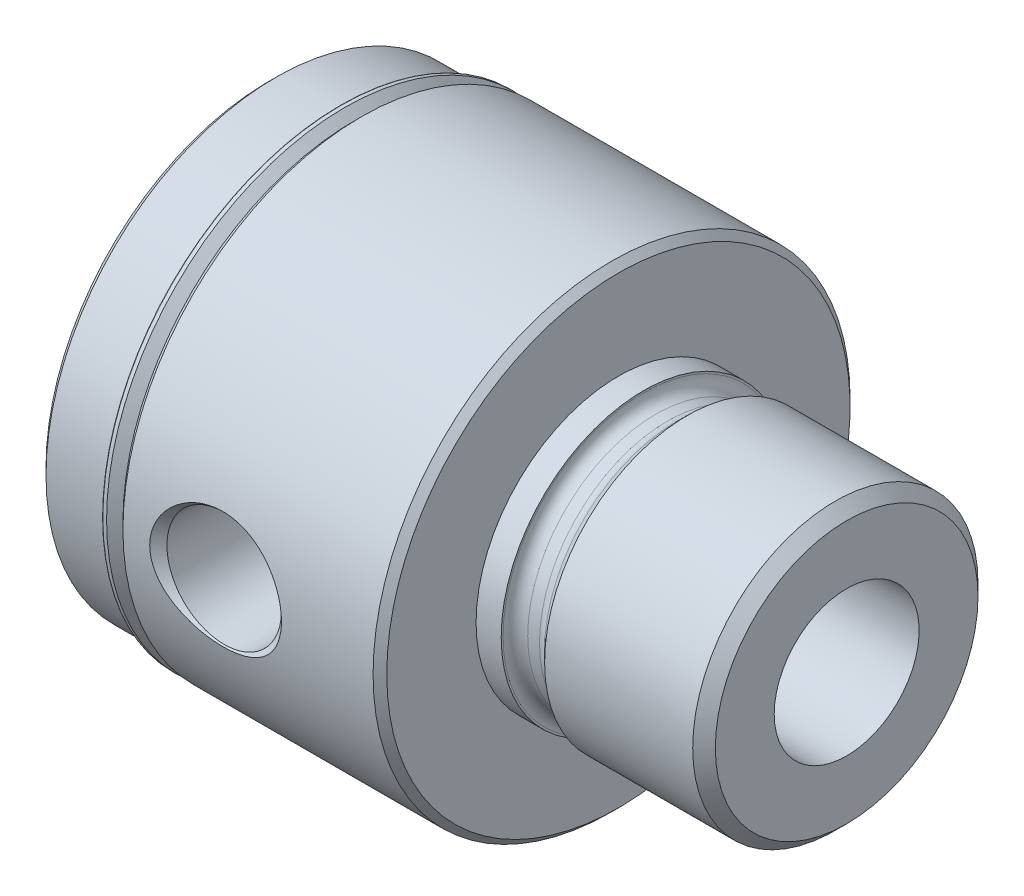
SolidWorks part; units mm, degrees
ref_plane "Front Plane" through (0, 0, 0) normal (0, 0, 1) x (1, 0, 0)
ref_plane "Top Plane" through (0, 0, 0) normal (0, 1, 0) x (1, 0, 0)
ref_plane "Right Plane" through (0, 0, 0) normal (1, 0, 0) x (0, 0, -1)
sketch "Sketch1" plane through (0, 0, 0) normal (0, 0, 1) x (1, 0, 0)
  line L0 (-38.8874, 0) -> (-38.8874, 24.8158)
  line L1 (-38.8874, 24.8158) -> (-38.1254, 25.5778)
  line L2 (-38.1254, 25.5778) -> (-31.496, 25.5778)
  line L3 (-31.496, 25.5778) -> (-30.4292, 24.511)
  line L4 (-30.4292, 24.511) -> (-29.3624, 24.511)
  line L5 (-29.3624, 24.511) -> (-29.3624, 25.781)
  line L6 (-29.3624, 25.781) -> (-28.6004, 26.543)
  line L7 (-28.6004, 26.543) -> (-0.762, 26.543)
  line L8 (-0.762, 26.543) -> (0, 25.781)
  line L9 (0, 25.781) -> (0, 0)
  line L10 (0, 0) -> (-38.8874, 0)
  line L11 (0, 0) -> (-38.8874, 0) construction
revolve "Revolve1" add sketch "Sketch1" angle 360 about L11 reverse direction yes
sketch "Sketch2" plane through (0, 0, 0) normal (0, 0, 1) x (1, 0, 0)
  line L0 (0, 0) -> (0, 15.8432)
  line L1 (0, 15.8432) -> (2.794, 15.8432)
  line L2 (2.794, 15.8432) -> (2.794, 15.6337)
  line L3 (4.1656, 14.2621) -> (5.4771, 14.2621)
  line L4 (6.4469, 14.6638) -> (7.6581, 15.875)
  line L5 (7.6581, 15.875) -> (24.1402, 15.875)
  line L6 (24.1402, 15.875) -> (25.4, 14.6152)
  line L7 (25.4, 14.6152) -> (25.4, 0)
  line L8 (25.4, 0) -> (0, 0)
  line L9 (25.4, 0) -> (0, 0) construction
  arc A0 (2.794, 15.6337) -> (4.1656, 14.2621) centre (4.1656, 15.6337) ccw
  arc A1 (5.4771, 14.2621) -> (6.4469, 14.6638) centre (5.4771, 15.6337) ccw
revolve "Revolve2" add sketch "Sketch2" angle 360 about L9 reverse direction yes
cosmetic thread "Cosmetic Thread1" parameters "D1"=18.9531, "D2"=29.2303
sketch "Sketch3" plane through (0, 0, 0) normal (0, 1, 0) x (1, 0, 0)
  line L0 (-18.288, 0) -> (-12.6123, -3.2768)
  line L1 (-12.6123, -3.2768) -> (-11.9159, -25.5856)
  line L2 (-11.9159, -25.5856) -> (-10.9585, -26.543)
  line L3 (-10.9585, -26.543) -> (-10.9585, -29.083)
  line L4 (-10.9585, -29.083) -> (-18.288, -29.083)
  line L5 (-18.288, -29.083) -> (-18.288, 0)
  line L6 (-18.288, -29.083) -> (-18.288, 0) construction
revolve "Cut-Revolve1" cut sketch "Sketch3" angle 360 about L6 reverse direction yes
cosmetic thread "Cosmetic Thread2" parameters "D1"=20.574, "D2"=40.1763
sketch "Sketch4" plane through (0, 0, 0) normal (0, 0, 1) x (1, 0, 0)
  line L0 (-30.9438, 26.3188) -> (-28.8128, 24.1877)
  line L1 (-28.8128, 24.1877) -> (-28.4895, 24.511)
  line L2 (-28.4895, 24.511) -> (-30.4707, 26.4922)
  line L3 (-30.4707, 26.4922) -> (-30.872, 26.4922)
  line L4 (-30.4707, 0) -> (-31.1172, 0) construction
  arc A0 (-30.872, 26.4922) -> (-30.9438, 26.3188) centre (-30.872, 26.3906) ccw
revolve "Revolve3" add sketch "Sketch4" angle 360 about L4 reverse direction yes
ref_plane "Plane1" through (-26.1874, 0, 0) normal (1, 0, 0) x (0, 0, -1)
ref_plane "Plane2" through (35.0266, 0, 0) normal (1, 0, 0) x (0, 0, -1)
ref_plane "Plane3" through (15.9766, 0, 0) normal (1, 0, 0) x (0, 0, -1)
ref_plane "Plane4" through (-9.4234, 0, 0) normal (1, 0, 0) x (0, 0, -1)
ref_plane "Plane5" through (-9.4234, 0, 0) normal (1, 0, 0) x (0, 0, -1)
sketch "Sketch5" plane through (0, 0, 0) normal (0, 0, 1) x (1, 0, 0)
  line L0 (-38.8874, 0) -> (-38.8874, 8.0645)
  line L1 (-38.8874, 8.0645) -> (35.052, 8.0645)
  line L2 (35.052, 8.0645) -> (35.052, 0)
  line L3 (35.052, 0) -> (-38.8874, 0)
  line L4 (35.052, 0) -> (-38.8874, 0) construction
revolve "Cut-Revolve2" cut sketch "Sketch5" angle 360 about L4 reverse direction yes
ref_plane "Plane6" through (-38.8874, 0, 0) normal (1, 0, 0) x (0, 0, -1)
ref_plane "Plane7" through (25.4, 0, 0) normal (1, 0, 0) x (0, 0, -1)
ref_plane "Plane8" through (25.4, 0, 0) normal (1, 0, 0) x (0, 0, -1)
ref_plane "Plane9" through (0, 0, 0) normal (0, 0, 1) x (1, 0, 0)
ref_plane "Plane10" through (0, 0, 0) normal (1, 0, 0) x (0, 0, -1)
ref_plane "Plane11" through (25.4, 0, 0) normal (1, 0, 0) x (0, 0, -1)
ref_plane "e2 XY" through (0, 0, 0) normal (0, 0, 1) x (1, 0, 0)
ref_plane "e2 XZ" through (0, 0, 0) normal (0, -1, 0) x (-1, 0, 0)
ref_plane "e2 YZ" through (-18.288, 0, 0) normal (1, 0, 0) x (0, 0, -1)
ref_axis "e2 X" through (-80.9, 0, 0) along (1, 0, 0)
ref_axis "e2 Y" through (-18.288, -50, 0) along (0, 1, 0)
ref_axis "e2 Z" through (-18.288, 0, 80.9) along (0, 0, -1)
sketch3d "e2"
  point P0 (-18.288, 0, 0)
ref_plane "g2 XY" through (0, 0, 0) normal (0, 0, 1) x (1, 0, 0)
ref_plane "g2 XZ" through (0, 0, 0) normal (0, -1, 0) x (-1, 0, 0)
ref_plane "g2 YZ" through (25.4, 0, 0) normal (1, 0, 0) x (0, 0, -1)
ref_axis "g2 X" through (-80.9, 0, 0) along (1, 0, 0)
ref_axis "g2 Y" through (25.4, -50, 0) along (0, 1, 0)
ref_axis "g2 Z" through (25.4, 0, 80.9) along (0, 0, -1)
sketch3d "g2"
  point P0 (25.4, 0, 0)
ref_plane "h1 XY" through (0, 0, 0) normal (0, 0, 1) x (1, 0, 0)
ref_plane "h1 XZ" through (0, 0, 0) normal (0, -1, 0) x (-1, 0, 0)
ref_plane "h1 YZ" through (0, 0, 0) normal (1, 0, 0) x (0, 0, -1)
ref_axis "h1 X" through (-80.9, 0, 0) along (1, 0, 0)
ref_axis "h1 Y" through (0, -50, 0) along (0, 1, 0)
ref_axis "h1 Z" through (0, 0, 80.9) along (0, 0, -1)
sketch3d "h1"
  point P0 (0, 0, 0)
ref_plane "h2 XY" through (0, 0, 0) normal (0, 0, 1) x (1, 0, 0)
ref_plane "h2 XZ" through (0, 0, 0) normal (0, -1, 0) x (-1, 0, 0)
ref_plane "h2 YZ" through (2.794, 0, 0) normal (1, 0, 0) x (0, 0, -1)
ref_axis "h2 X" through (-80.9, 0, 0) along (1, 0, 0)
ref_axis "h2 Y" through (2.794, -50, 0) along (0, 1, 0)
ref_axis "h2 Z" through (2.794, 0, 80.9) along (0, 0, -1)
sketch3d "h2"
  point P0 (2.794, 0, 0)
ref_plane "k1 XY" through (0, 0, 0) normal (0, 0, 1) x (1, 0, 0)
ref_plane "k1 XZ" through (0, 15.875, 0) normal (0, -1, 0) x (-1, 0, 0)
ref_plane "k1 YZ" through (25.4, 0, 0) normal (1, 0, 0) x (0, 0, -1)
ref_axis "k1 X" through (-80.9, 15.875, 0) along (1, 0, 0)
ref_axis "k1 Y" through (25.4, -50, 0) along (0, 1, 0)
ref_axis "k1 Z" through (25.4, 15.875, 80.9) along (0, 0, -1)
sketch3d "k1"
  point P0 (25.4, 15.875, 0)
ref_plane "k2 XY" through (0, 0, 0) normal (0, 0, 1) x (1, 0, 0)
ref_plane "k2 XZ" through (0, -15.875, 0) normal (0, -1, 0) x (-1, 0, 0)
ref_plane "k2 YZ" through (25.4, 0, 0) normal (1, 0, 0) x (0, 0, -1)
ref_axis "k2 X" through (-80.9, -15.875, 0) along (1, 0, 0)
ref_axis "k2 Y" through (25.4, -50, 0) along (0, 1, 0)
ref_axis "k2 Z" through (25.4, -15.875, 80.9) along (0, 0, -1)
sketch3d "k2"
  point P0 (25.4, -15.875, 0)
ref_plane "l1 XY" through (0, 0, 0) normal (0, 0, 1) x (1, 0, 0)
ref_plane "l1 XZ" through (0, 15.8432, 0) normal (0, -1, 0) x (-1, 0, 0)
ref_plane "l1 YZ" through (0, 0, 0) normal (1, 0, 0) x (0, 0, -1)
ref_axis "l1 X" through (-80.9, 15.8432, 0) along (1, 0, 0)
ref_axis "l1 Y" through (0, -50, 0) along (0, 1, 0)
ref_axis "l1 Z" through (0, 15.8432, 80.9) along (0, 0, -1)
sketch3d "l1"
  point P0 (0, 15.8432, 0)
ref_plane "l2 XY" through (0, 0, 0) normal (0, 0, 1) x (1, 0, 0)
ref_plane "l2 XZ" through (0, -15.8432, 0) normal (0, -1, 0) x (-1, 0, 0)
ref_plane "l2 YZ" through (0, 0, 0) normal (1, 0, 0) x (0, 0, -1)
ref_axis "l2 X" through (-80.9, -15.8432, 0) along (1, 0, 0)
ref_axis "l2 Y" through (0, -50, 0) along (0, 1, 0)
ref_axis "l2 Z" through (0, -15.8432, 80.9) along (0, 0, -1)
sketch3d "l2"
  point P0 (0, -15.8432, 0)
ref_plane "lovra XY" through (0, 0, 0) normal (1, 0, 0) x (0, 0, -1)
ref_plane "lovra XZ" through (0, 0, 0) normal (0, -1, 0) x (-1, 0, 0)
ref_plane "lovra YZ" through (0, 0, 0) normal (0, 0, -1) x (-1, 0, 0)
ref_axis "lovra X" through (0, 0, 80.9) along (0, 0, -1)
ref_axis "lovra Y" through (0, -50, 0) along (0, 1, 0)
ref_axis "lovra Z" through (80.9, 0, 0) along (-1, 0, 0)
sketch3d "lovra"
  point P0 (0, 0, 0)
ref_plane "to_ft XY" through (0, 0, 0) normal (0, 1, 0) x (1, 0, 0)
ref_plane "to_ft XZ" through (0, 0, 36.957) normal (0, 0, 1) x (1, 0, 0)
ref_plane "to_ft YZ" through (-18.288, 0, 0) normal (1, 0, 0) x (0, 0, -1)
ref_axis "to_ft X" through (-80.9, 0, 36.957) along (1, 0, 0)
ref_axis "to_ft Y" through (-18.288, 0, 50) along (0, 0, -1)
ref_axis "to_ft Z" through (-18.288, 50, 36.957) along (0, -1, 0)
sketch3d "to_ft"
  point P0 (-18.288, 0, 36.957)
ref_plane "to_nut XY" through (0, 0, 0) normal (1, 0, 0) x (0, 0, -1)
ref_plane "to_nut XZ" through (0, 0, 0) normal (0, -1, 0) x (-1, 0, 0)
ref_plane "to_nut YZ" through (0, 0, 0) normal (0, 0, -1) x (-1, 0, 0)
ref_axis "to_nut X" through (0, 0, 80.9) along (0, 0, -1)
ref_axis "to_nut Y" through (0, -50, 0) along (0, 1, 0)
ref_axis "to_nut Z" through (80.9, 0, 0) along (-1, 0, 0)
sketch3d "to_nut"
  point P0 (0, 0, 0)
ref_plane "to_stud XY" through (25.4, 0, 0) normal (-1, 0, 0) x (0, 0, 1)
ref_plane "to_stud XZ" through (0, 0, 0) normal (0, 1, 0) x (1, 0, 0)
ref_plane "to_stud YZ" through (0, 0, 0) normal (0, 0, -1) x (-1, 0, 0)
ref_axis "to_stud X" through (25.4, 0, 80.9) along (0, 0, -1)
ref_axis "to_stud Y" through (25.4, 50, 0) along (0, -1, 0)
ref_axis "to_stud Z" through (-80.9, 0, 0) along (1, 0, 0)
sketch3d "to_stud"
  point P0 (25.4, 0, 0)
ref_plane "to_stud_1 XY" through (25.4, 0, 0) normal (-1, 0, 0) x (0, 0, 1)
ref_plane "to_stud_1 XZ" through (0, 0, 0) normal (0, 1, 0) x (1, 0, 0)
ref_plane "to_stud_1 YZ" through (0, 0, 0) normal (0, 0, -1) x (-1, 0, 0)
ref_axis "to_stud_1 X" through (25.4, 0, 80.9) along (0, 0, -1)
ref_axis "to_stud_1 Y" through (25.4, 50, 0) along (0, -1, 0)
ref_axis "to_stud_1 Z" through (-80.9, 0, 0) along (1, 0, 0)
sketch3d "to_stud_1"
  point P0 (25.4, 0, 0)
ref_plane "to_stud_trans XY" through (25.4, 0, 0) normal (-1, 0, 0) x (0, 0, 1)
ref_plane "to_stud_trans XZ" through (0, 0, 0) normal (0, 1, 0) x (1, 0, 0)
ref_plane "to_stud_trans YZ" through (0, 0, 0) normal (0, 0, -1) x (-1, 0, 0)
ref_axis "to_stud_trans X" through (25.4, 0, 80.9) along (0, 0, -1)
ref_axis "to_stud_trans Y" through (25.4, 50, 0) along (0, -1, 0)
ref_axis "to_stud_trans Z" through (-80.9, 0, 0) along (1, 0, 0)
sketch3d "to_stud_trans"
  point P0 (25.4, 0, 0)
ref_plane "to_tube XY" through (-38.8874, 0, 0) normal (1, 0, 0) x (0, 0, -1)
ref_plane "to_tube XZ" through (0, 0, 0) normal (0, -1, 0) x (-1, 0, 0)
ref_plane "to_tube YZ" through (0, 0, 0) normal (0, 0, -1) x (-1, 0, 0)
ref_axis "to_tube X" through (-38.8874, 0, 80.9) along (0, 0, -1)
ref_axis "to_tube Y" through (-38.8874, -50, 0) along (0, 1, 0)
ref_axis "to_tube Z" through (80.9, 0, 0) along (-1, 0, 0)
sketch3d "to_tube"
  point P0 (-38.8874, 0, 0)
